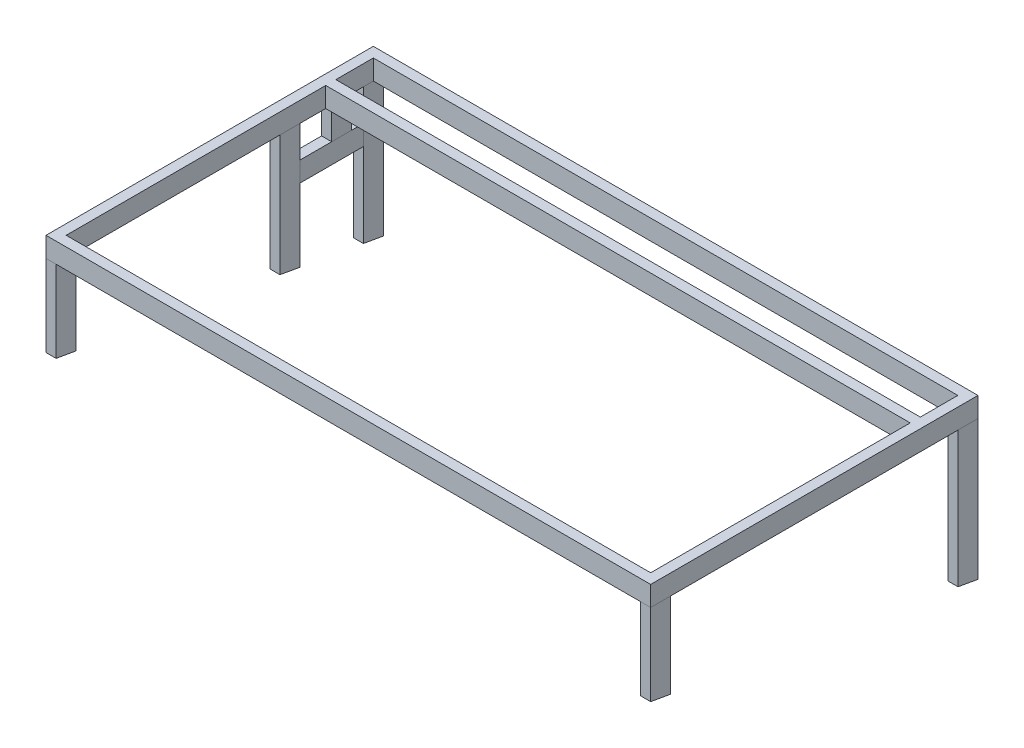
SolidWorks part; units mm, degrees
ref_plane "Front Plane" through (0, 0, 0) normal (0, 0, 1) x (1, 0, 0)
ref_plane "Top Plane" through (0, 0, 0) normal (0, 1, 0) x (1, 0, 0)
ref_plane "Right Plane" through (0, 0, 0) normal (1, 0, 0) x (0, 0, -1)
sketch "Sketch22" plane through (0, 0, 0) normal (0, 1, 0) x (1, 0, 0)
  line L0 (-736.6, 387.1) -> (736.6, 387.1)
  line L1 (-762, 412.5) -> (762, 412.5)
  line L2 (-762, 412.5) -> (-762, -412.5)
  line L3 (-762, -412.5) -> (762, -412.5)
  line L4 (762, 412.5) -> (762, -412.5)
  line L5 (-762, 412.5) -> (762, -412.5) construction
  line L6 (-762, -412.5) -> (762, 412.5) construction
  line L7 (736.6, 387.1) -> (736.6, -387.1)
  line L8 (-736.6, -387.1) -> (736.6, -387.1)
  line L9 (-736.6, 387.1) -> (-736.6, -387.1)
  point P0 (0, 0)
  dimension "D1" = 1524
  dimension "D2" = 825
  dimension "D3" = 25.4
extrude "Boss-Extrude3" add sketch "Sketch22" against normal blind 50.4
ref_plane "Plane1" through (0, -256, 0) normal (0, 1, 0) x (1, 0, 0)
ref_plane "Plane2" through (0, 0, 412.5) normal (0, 0, 1) x (1, 0, 0)
ref_axis "Axis1" through (-838.2, -256, 412.5) along (1, 0, 0)
ref_plane "LAUNCH PLANE" through (0, -318.8223, 56.217) normal (0, 0.9848, -0.1736) x (1, 0, 0)
sketch "Sketch23" plane through (0, -50.4, 0) normal (0, -1, 0) x (1, 0, 0)
  line L0 (-736.6, -387.1) -> (-736.6, 387.1) construction
  line L1 (-762, 412.5) -> (-736.6, 412.5)
  line L2 (-762, 412.5) -> (-762, 362.1)
  line L3 (-762, 362.1) -> (-736.6, 362.1)
  line L4 (-736.6, 412.5) -> (-736.6, 362.1)
  line L5 (0, 0) -> (0, 277.5925) construction
  line L6 (736.6, 412.5) -> (736.6, 362.1)
  line L7 (762, 362.1) -> (736.6, 362.1)
  line L8 (762, 412.5) -> (762, 362.1)
  line L9 (762, 412.5) -> (736.6, 412.5)
  dimension "D1" = 50.4
extrude "Boss-Extrude4" add sketch "Sketch23" along normal up to surface (205.6 mm away) separate body up to plane "LAUNCH PLANE"
sketch "Sketch24" plane through (0, -50.4, 0) normal (0, -1, 0) x (1, 0, 0)
  line L0 (-736.6, -387.1) -> (-736.6, 387.1) construction
  line L1 (-762, -412.5) -> (-736.6, -412.5)
  line L2 (-762, -412.5) -> (-762, -362.1)
  line L3 (-762, -362.1) -> (-736.6, -362.1)
  line L4 (-736.6, -412.5) -> (-736.6, -362.1)
  line L5 (0, 0) -> (0, -131.3731) construction
  line L6 (736.6, -412.5) -> (736.6, -362.1)
  line L7 (762, -362.1) -> (736.6, -362.1)
  line L8 (762, -412.5) -> (762, -362.1)
  line L9 (762, -412.5) -> (736.6, -412.5)
  line L10 (-762, -412.5) -> (-762, 412.5) construction
  line L16 (-736.6, -202.1) -> (-762, -202.1)
  line L17 (-736.6, -202.1) -> (-736.6, -151.7)
  line L18 (-736.6, -151.7) -> (-762, -151.7)
  line L19 (-762, -202.1) -> (-762, -151.7)
  dimension "D1" = 50.4
  dimension "D2" = 160
  dimension "D3" = 50.4
extrude "Boss-Extrude5" add sketch "Sketch24" along normal up to surface (351.0698 mm away) separate body up to plane "LAUNCH PLANE"
sketch "Sketch26" plane through (0, 0, 0) normal (0, 1, 0) x (1, 0, 0)
  line L0 (-736.6, 387.1) -> (-736.6, -387.1) construction
  line L1 (-736.6, 292.5) -> (736.6, 292.5)
  line L2 (-736.6, 292.5) -> (-736.6, 267.1)
  line L3 (-736.6, 267.1) -> (736.6, 267.1)
  line L4 (736.6, 292.5) -> (736.6, 267.1)
  line L5 (736.6, -387.1) -> (736.6, 387.1) construction
  line L7 (736.6, 387.1) -> (-736.6, 387.1) construction
  dimension "D1" = 25.4
  dimension "D2" = 120
extrude "Boss-Extrude6" add sketch "Sketch26" against normal up to surface (50.4 mm away) up to face at (0, -50.4, 0)
sketch "Sketch25" plane through (762, 0, 0) normal (1, 0, 0) x (0, 0, -1)
  line L0 (362.1, -394.143) -> (412.5, -403.0299)
  line L2 (362.1, -392.5829) -> (362.1, -50.4) construction
  line L3 (412.5, -401.4698) -> (412.5, -50.4) construction
  line L4 (412.5, -403.0299) -> (412.5, -401.4698)
  line L5 (412.5, -401.4698) -> (-412.5, -401.4698)
  line L6 (-412.5, -401.4698) -> (-412.5, -257.5601)
  line L7 (-412.5, -256) -> (-412.5, -50.4) construction
  line L8 (-412.5, -257.5601) -> (-362.1, -266.447)
  line L9 (-362.1, -264.8869) -> (-362.1, -50.4) construction
  line L10 (-362.1, -266.447) -> (-362.1, -264.8869)
  line L11 (-362.1, -264.8869) -> (362.1, -394.143)
  line L12 (412.5, -50.4) -> (362.1, -50.4) construction
  dimension "D1" = 207.1601
  dimension "D2" = 216.047
sketch "Sketch27" plane through (0, 0, -202.1) normal (0, 0, -1) x (-1, 0, 0)
  line L0 (736.6, -401.4698) -> (736.6, -50.4) construction
  line L1 (736.6, -130.4) -> (762, -130.4)
  line L2 (736.6, -130.4) -> (736.6, -180.8)
  line L3 (736.6, -180.8) -> (762, -180.8)
  line L4 (762, -130.4) -> (762, -180.8)
  line L5 (762, -401.4698) -> (762, -50.4) construction
  line L6 (762, -50.4) -> (736.6, -50.4) construction
  dimension "D1" = 50.4
  dimension "D2" = 80
extrude "Boss-Extrude7" add sketch "Sketch27" along normal up to surface (160 mm away) separate body up to face at (-749.3, -221.4914, -362.1)
sketch "Sketch29" plane through (0, -50.4, 0) normal (0, -1, 0) x (1, 0, 0)
  line L0 (-736.6, -387.1) -> (-736.6, -292.5) construction
  line L1 (-736.6, -332.5) -> (-762, -332.5)
  line L2 (-736.6, -332.5) -> (-736.6, -282.1)
  line L3 (-736.6, -282.1) -> (-762, -282.1)
  line L4 (-762, -332.5) -> (-762, -282.1)
  line L5 (-762, -362.1) -> (-762, -202.1) construction
  line L6 (-736.6, -202.1) -> (-762, -202.1) construction
  dimension "D1" = 50.4
  dimension "D2" = 80
extrude "Boss-Extrude8" add sketch "Sketch29" along normal up to surface (80 mm away) separate body up to face at (-749.3, -130.4, -282.1)
